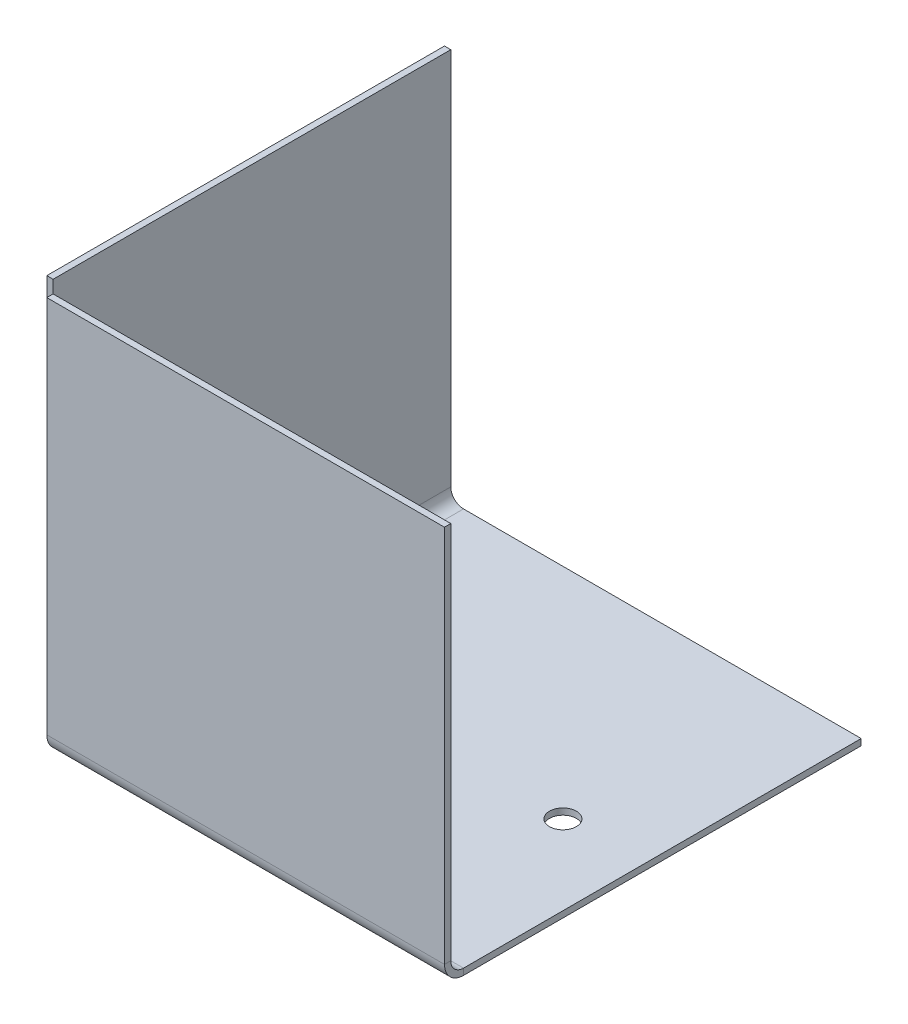
SolidWorks part; units mm, degrees
note: The reader was unsure of these and kept them because the rebuilt part matched: thickness of "Base-Flange1", "Edge-Flange1", "Edge-Flange2", "Sheet-Metal1", "Sheet-Metal2", "Sheet-Metal3", "Sheet-Metal5", "Sheet-Metal6"; flange length of "Edge-Flange1", "Edge-Flange2".
material "Alumina"
ref_plane "Front Plane" through (0, 0, 0) normal (0, 0, 1) x (1, 0, 0)
ref_plane "Top Plane" through (0, 0, 0) normal (0, 1, 0) x (1, 0, 0)
ref_plane "Right Plane" through (0, 0, 0) normal (1, 0, 0) x (0, 0, -1)
sketch "Sketch1" plane through (0, 0, 0) normal (0, 1, 0) x (1, 0, 0)
  line L1 (-50, 50) -> (50, 50)
  line L2 (-50, 50) -> (-50, -50)
  line L3 (-50, -50) -> (50, -50)
  line L4 (50, 50) -> (50, -50)
  line L5 (-50, 50) -> (50, -50) construction
  line L6 (-50, -50) -> (50, 50) construction
  point P0 (0, 0)
  dimension "D1" = 100
  dimension "D2" = 100
base flange "Base-Flange1" sketch "Sketch1" thickness 1.5875 reverse thickness direction no parameters "D1"=3.2
edge flange "Edge-Flange1" sketch "Sketch10" flange angle 90 flange length 100 flange position bend outside bend radius 3.2 thickness 1.5875 relief rectangular parameters "D1"=19.05, "D6"=10
sketch "Sketch10" plane through (-50, 0, 0) normal (-1, 0, 0) x (0, 0, 1)
  line L0 (-50, 0) -> (50, 0) construction
  line L1 (-50, 0) -> (50, 0)
  line L2 (-50, 0) -> (-50, 98.4125)
  line L3 (-50, 98.4125) -> (50, 98.4125)
  line L4 (50, 98.4125) -> (50, 0)
bend "EdgeBend1" bend radius 3.2 bend angle 90 parameters "D5"=1
edge flange "Edge-Flange2" sketch "Sketch13" flange angle 90 flange length 100 flange position bend outside bend radius 3.2 thickness 1.5875 relief rectangular parameters "D1"=19.05, "D6"=10
sketch "Sketch13" plane through (0, 0, 50) normal (0, 0, 1) x (1, 0, 0)
  line L2 (-50, 0) -> (-50, 98.4125)
  line L3 (-50, 98.4125) -> (50, 98.4125)
  line L4 (50, 98.4125) -> (50, 0)
  line L7 (-50, 0) -> (50, 0) construction
  line L8 (-50, 0) -> (50, 0)
bend "EdgeBend2" bend radius 3.2 bend angle 90 parameters "D5"=2
hole_wizard "1/4 Clearance Hole1" positions "Sketch17" profile "Sketch19" hole size "1/4" standard "ANSI Inch" end condition through all
sketch "Sketch17" plane through (0, 0, 0) normal (0, 1, 0) x (1, 0, 0)
  line L0 (-50, -50) -> (50, -50) construction
  line L1 (-50, 50) -> (-50, -50) construction
  line L2 (50, -50) -> (50, 50) construction
  point P0 (-30, -5)
  point P2 (30, -5)
  dimension "D1" = 45
  dimension "D2" = 20
  dimension "D3" = 20
sketch "Sketch19" plane through (-30, 0, 5) normal (1, 0, 0) x (0, 0, 1)
  line L0 (0, 0) -> (0, 1.5875)
  line L1 (0, 1.5875) -> (3.3782, 1.5875)
  line L2 (3.3782, 1.5875) -> (3.3782, 0)
  line L5 (3.3782, 0) -> (0, 0)
  line L11 (0, -6.35) -> (0, 107.95) construction
  dimension "Thru Hole Dia." = 6.7564
  dimension "Thru Hole Depth" = 1.5875
hole_wizard "1/4 Clearance Hole2" [suppressed] positions "Sketch20" profile "Sketch21" hole size "1/4" standard "ANSI Inch"
sketch "Sketch20" plane through (0, 0, 0) normal (0, 1, 0) x (1, 0, 0)
  line L0 (-50, 50) -> (-50, -50) construction
  line L1 (-50, -50) -> (50, -50) construction
  line L2 (50, 50) -> (-50, 50) construction
  point P0 (-5, -30)
  point P2 (-5, 30)
  dimension "D1" = 45
  dimension "D2" = 20
  dimension "D3" = 20
sketch "Sketch21" plane through (-5, 0, 30) normal (1, 0, 0) x (0, 0, 1)
  line L0 (0, 0) -> (0, 1.5875)
  line L1 (0, 1.5875) -> (3.3782, 1.5875)
  line L2 (3.3782, 1.5875) -> (3.3782, 0)
  line L5 (3.3782, 0) -> (0, 0)
  line L11 (0, -6.35) -> (0, 107.95) construction
  dimension "Thru Hole Dia." = 6.7564
  dimension "Thru Hole Depth" = 1.5875
sketch "Bend-Lines1" [suppressed] plane through (0, 0, 0) normal (0, 1, 0) x (1, 0, 0)
sketch "Bounding-Box1" [suppressed] plane through (0, 0, 0) normal (0, 1, 0) x (1, 0, 0)
sheet metal parameters "Sheet-Metal1" thickness 1.5875 parameters "D1"=0.7366, "D7"=19.05
flat pattern "Flat-Pattern1" [suppressed]
sketch "Bend-Lines2" plane through (0, 0, 0) normal (0, 1, 0) x (1, 0, 0)
sketch3d "Bounding-Box2" [suppressed]
  line L0 (-50, -50, 0) -> (50, -50, 0) construction
  line L1 (-50, 50, 0) -> (50, 50, 0) construction
  line L2 (-50, -50, 0) -> (-50, 50, 0) construction
  line L3 (50, -50, 0) -> (50, 50, 0) construction
sheet metal parameters "Sheet-Metal2" thickness 1.5875 parameters "D1"=0.7366, "D7"=19.05
flat pattern "Flat-Pattern1"
sketch "Bend-Lines2" plane through (0, 0, 0) normal (0, 1, 0) x (1, 0, 0)
  line L0 (-57.3228, 50) -> (-57.3228, -50) construction
  line L1 (-57.3228, 50) -> (-57.3228, -50) construction
sketch3d "Bounding-Box2" [suppressed]
  line L0 (50, -50, 0) -> (-145.5957, -50, 0) construction
  line L1 (50, 50, 0) -> (-145.5957, 50, 0) construction
  line L2 (50, -50, 0) -> (50, 50, 0) construction
  line L3 (-145.5957, -50, 0) -> (-145.5957, 50, 0) construction
bend of the flat pattern "Flatten-<EdgeBend1>1"
sheet metal parameters "Sheet-Metal3" thickness 1.5875 parameters "D1"=0.7366, "D7"=19.05
flat pattern "Flat-Pattern1"
sketch "Bend-Lines2" plane through (0, 0, 0) normal (0, 1, 0) x (1, 0, 0)
  line L0 (-67.4555, 50) -> (-67.4555, -50) construction
  line L1 (-67.4555, 50) -> (-67.4555, -50) construction
  line L2 (-50, -67.4555) -> (50, -67.4555) construction
  line L3 (-50, -67.4555) -> (50, -67.4555) construction
sketch3d "Bounding-Box2" [suppressed]
  line L0 (50, -159.5109, 0) -> (-159.5109, -159.5109, 0) construction
  line L1 (50, 50, 0) -> (-159.5109, 50, 0) construction
  line L2 (50, -159.5109, 0) -> (50, 50, 0) construction
  line L3 (-159.5109, -159.5109, 0) -> (-159.5109, 50, 0) construction
bend of the flat pattern "Flatten-<EdgeBend1>1"
bend of the flat pattern "Flatten-<EdgeBend2>1"
sheet metal parameters "Sheet-Metal5" thickness 1.5875 parameters "D1"=0.7366, "D7"=19.05
flat pattern "Flat-Pattern1"
sketch "Bend-Lines2" plane through (0, 0, 0) normal (0, 1, 0) x (1, 0, 0)
  line L0 (-53.1367, 50) -> (-53.1367, -50) construction
  line L1 (-53.1367, 50) -> (-53.1367, -50) construction
  line L2 (-50, -53.1367) -> (50, -53.1367) construction
  line L3 (-50, -53.1367) -> (50, -53.1367) construction
sketch3d "Bounding-Box2" [suppressed]
  line L0 (-151.4859, 50, 0) -> (-151.4859, -151.4859, 0) construction
  line L1 (50, 50, 0) -> (50, -151.4859, 0) construction
  line L2 (-151.4859, 50, 0) -> (50, 50, 0) construction
  line L3 (-151.4859, -151.4859, 0) -> (50, -151.4859, 0) construction
bend of the flat pattern "Flatten-<EdgeBend1>1"
bend of the flat pattern "Flatten-<EdgeBend2>1"
sheet metal parameters "Sheet-Metal6" thickness 1.5875 parameters "D1"=0.7366, "D7"=19.05
flat pattern "Flat-Pattern1"
sketch "Bend-Lines2" plane through (0, 0, 0) normal (0, 1, 0) x (1, 0, 0)
  line L0 (-53.1367, 50) -> (-53.1367, -50) construction
  line L1 (-53.1367, 50) -> (-53.1367, -50) construction
  line L2 (-50, -53.1367) -> (50, -53.1367) construction
  line L3 (-50, -53.1367) -> (50, -53.1367) construction
sketch3d "Bounding-Box2" [suppressed]
  line L0 (-151.4859, 50, 0) -> (-151.4859, -151.4859, 0) construction
  line L1 (50, 50, 0) -> (50, -151.4859, 0) construction
  line L2 (-151.4859, 50, 0) -> (50, 50, 0) construction
  line L3 (-151.4859, -151.4859, 0) -> (50, -151.4859, 0) construction
bend of the flat pattern "Flatten-<EdgeBend1>1"
bend of the flat pattern "Flatten-<EdgeBend2>1"
